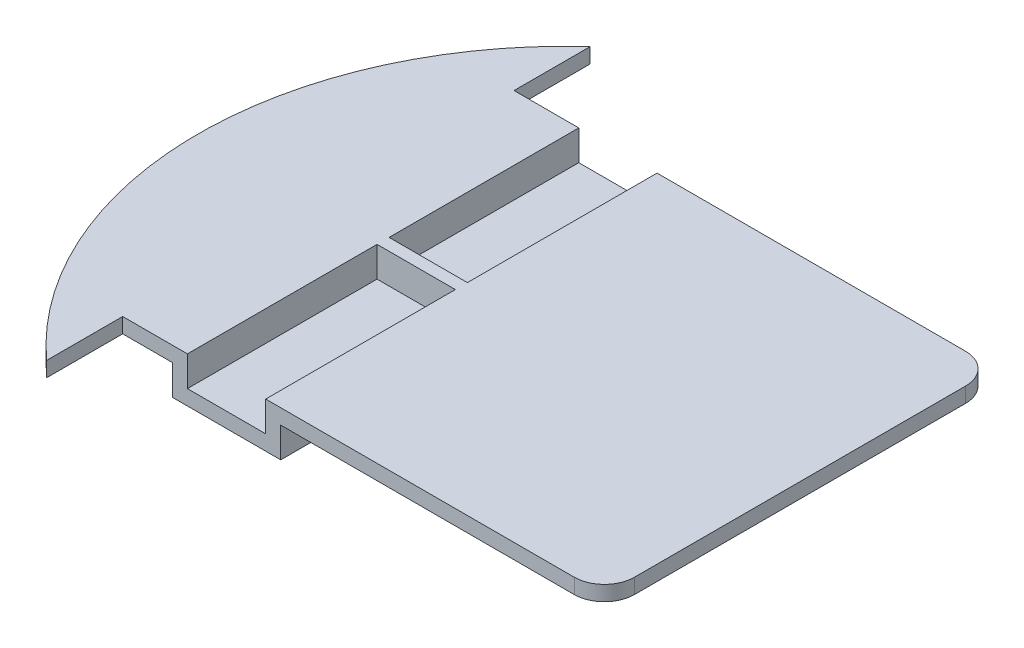
SolidWorks part; units mm, degrees
ref_plane "Front Plane" through (0, 0, 0) normal (0, 0, 1) x (1, 0, 0)
ref_plane "Top Plane" through (0, 0, 0) normal (0, 1, 0) x (1, 0, 0)
ref_plane "Right Plane" through (0, 0, 0) normal (1, 0, 0) x (0, 0, -1)
sketch "Sketch1" plane through (0, 0, 0) normal (0, 1, 0) x (1, 0, 0)
  line L0 (40.3018, 25) -> (110.3018, 25)
  line L4 (200.3018, 25) -> (200.3018, 155)
  line L6 (40.3018, 180.2747) -> (40.3018, 155)
  line L7 (40.3018, 155) -> (110.3018, 155)
  line L9 (40.3018, 25) -> (40.3018, -0.2747)
  line L12 (110.3018, 25) -> (200.3018, 25)
  line L13 (110.3018, 155) -> (200.3018, 155)
  arc A0 (40.3018, 180.2747) -> (40.3018, -0.2747) centre (122.1708, 90) ccw
  point P0 (0.3018, 90)
  dimension "D1" = 160
  dimension "D2" = 200
extrude "Boss-Extrude1" add sketch "Sketch1" along normal blind 5
fillet "Fillet1" radius 10 2 edges at (200.3018, 2.5, -155) (200.3018, 2.5, -25)
sketch "Sketch2" plane through (0, 0, -25) normal (0, 0, 1) x (1, 0, 0)
  line L1 (56.8018, 5) -> (92.8018, 5)
  line L2 (56.8018, 5) -> (56.8018, -10)
  line L3 (56.8018, -10) -> (92.8018, -10)
  line L4 (92.8018, 5) -> (92.8018, -10)
  line L5 (40.3018, 5) -> (40.3018, 0) construction
  line L6 (40.3018, 5) -> (190.3018, 5) construction
  dimension "D1" = 15
  dimension "D2" = 36
  dimension "D3" = 16.5
extrude "Boss-Extrude2" add sketch "Sketch2" against normal blind 64
sketch "Sketch4" plane through (0, 0, -25) normal (0, 0, 1) x (1, 0, 0)
  line L0 (56.8018, 0) -> (56.8018, -10) construction
  line L1 (61.8018, 5) -> (87.8018, 5)
  line L2 (61.8018, 5) -> (61.8018, -5)
  line L3 (61.8018, -5) -> (87.8018, -5)
  line L4 (87.8018, 5) -> (87.8018, -5)
  line L5 (92.8018, -10) -> (92.8018, 0) construction
  line L6 (56.8018, -10) -> (92.8018, -10) construction
  line L7 (40.3018, 5) -> (190.3018, 5) construction
  dimension "D1" = 5
  dimension "D2" = 5
  dimension "D3" = 5
extrude "Cut-Extrude1" cut sketch "Sketch4" against normal blind 63
ref_plane "Plane1" through (0, 0, -90) normal (0, 0, 1) x (1, 0, 0)
mirror "Mirror1" about plane through (0, 0, -90) normal (0, 0, 1) of "Boss-Extrude2", "Cut-Extrude1"
